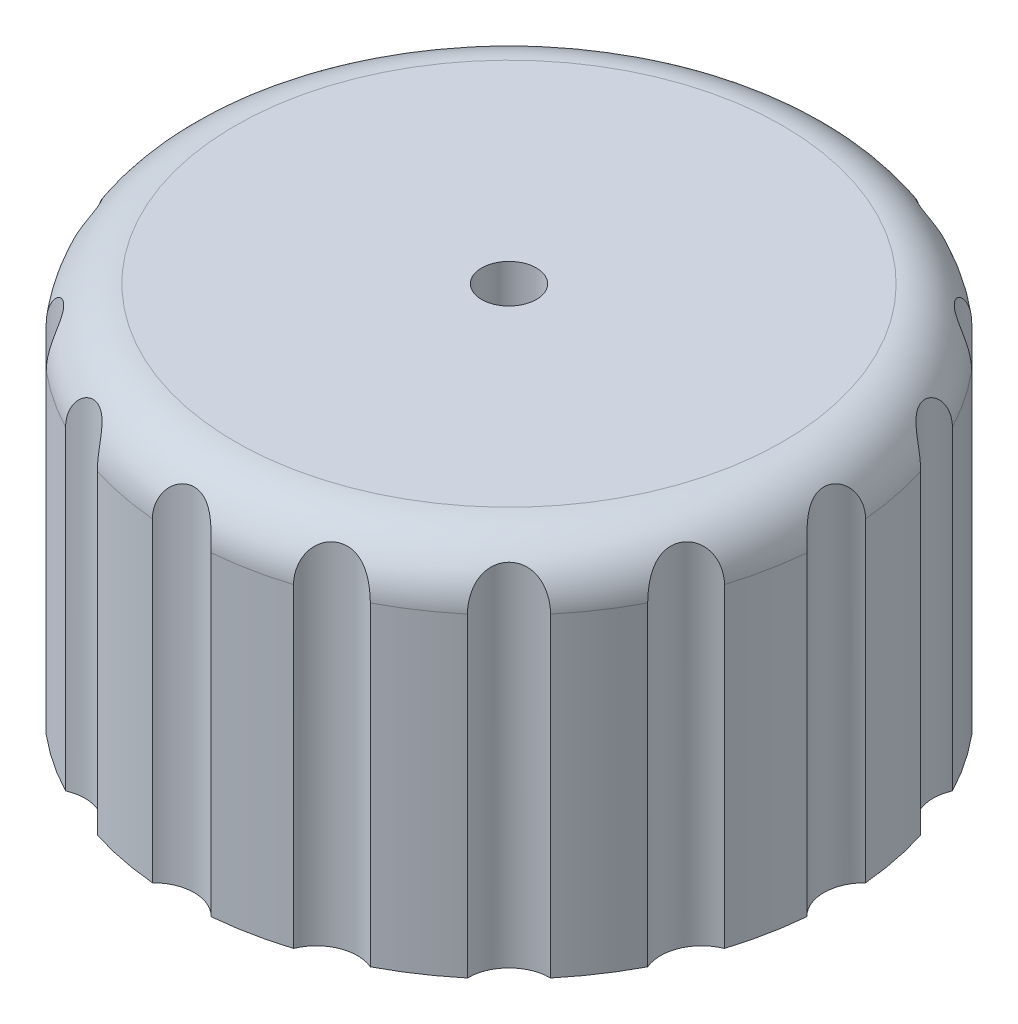
SolidWorks part; units mm, degrees
material "Delrin 2700 NC010, Low Viscosity Acetal Copolymer (SS)"
ref_plane "Front Plane" through (0, 0, 0) normal (0, 0, 1) x (1, 0, 0)
ref_plane "Top Plane" through (0, 0, 0) normal (0, 1, 0) x (1, 0, 0)
ref_plane "Right Plane" through (0, 0, 0) normal (1, 0, 0) x (0, 0, -1)
sketch "Sketch1" plane through (0, 0, 0) normal (0, 0, 1) x (1, 0, 0)
  line L0 (-2.765, 0) -> (-2.765, 2.8911)
  line L1 (-2.765, 2.8911) -> (0, 2.8911)
  line L2 (0, 2.8911) -> (0, 8)
  line L3 (0, 8) -> (-6, 8)
  line L4 (-6, 8) -> (-6, 1.2448)
  line L5 (-6, 1.2448) -> (-4.0034, 1.2448)
  line L6 (-4.0034, 1.2448) -> (-3.0676, 0)
  line L7 (-3.0676, 0) -> (-2.765, 0)
  dimension "D1" = 2.765
  dimension "D2" = 6
  dimension "D3" = 8
revolve "Revolve1" add sketch "Sketch1" angle 360 about L2
fillet "Fillet1" radius 1 1 edges at (0, 8, -6)
sketch "Sketch2" plane through (0, 0, 0) normal (0, 1, 0) x (1, 0, 0)
  circle A0 centre (0, 6.5) radius 0.75
  dimension "D2" = 1.5
  dimension "D1" = 6.5
extrude "Cut-Extrude1" cut sketch "Sketch2" along normal through all
pattern_circular "CirPattern1" count 16 over 360 about axis through (0, 8, 0) along (0, 1, 0) of "Cut-Extrude1"
sketch "Sketch3" plane through (0, 0, 0) normal (0, 1, 0) x (1, 0, 0)
  circle A0 centre (0, 0) radius 0.5
extrude "Cut-Extrude2" cut sketch "Sketch3" along normal through all
